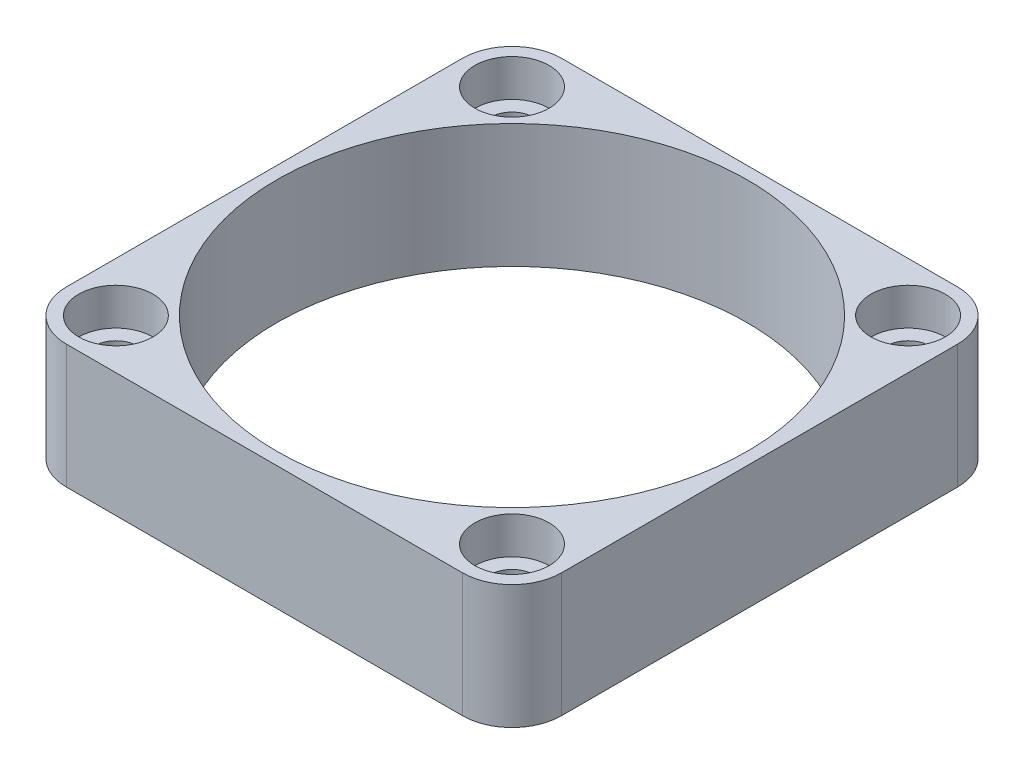
SolidWorks part; units mm, degrees
ref_plane "Front Plane" through (0, 0, 0) normal (0, 0, 1) x (1, 0, 0)
ref_plane "Top Plane" through (0, 0, 0) normal (0, 1, 0) x (1, 0, 0)
ref_plane "Right Plane" through (0, 0, 0) normal (1, 0, 0) x (0, 0, -1)
sketch "Sketch1" plane through (0, 0, 0) normal (0, 1, 0) x (1, 0, 0)
  line L1 (4, 0) -> (36, 0)
  line L2 (0, 4) -> (0, 36)
  line L3 (4, 40) -> (36, 40)
  line L4 (40, 4) -> (40, 36)
  arc A0 (4, 40) -> (0, 36) centre (4, 36) ccw
  arc A1 (0, 4) -> (4, 0) centre (4, 4) ccw
  arc A2 (40, 4) -> (36, 0) centre (36, 4) cw
  arc A3 (40, 36) -> (36, 40) centre (36, 36) ccw
  point P7 (0, 40)
  point P10 (0, 0)
  point P16 (4, 36)
  point P17 (36, 36)
  point P18 (36, 4)
  point P19 (4, 4)
  dimension "D2" = 4
  dimension "D1" = 40
extrude "Boss-Extrude1" add sketch "Sketch1" along normal blind 10
sketch "Sketch2" plane through (0, 10, 0) normal (0, 1, 0) x (1, 0, 0)
  line L0 (20, 0) -> (20, 40) construction
  line L1 (4, 0) -> (36, 0) construction
  line L2 (4, 40) -> (36, 40) construction
  line L3 (0, 20) -> (40, 20) construction
  line L4 (0, 4) -> (0, 36) construction
  line L5 (40, 4) -> (40, 36) construction
  circle A0 centre (4, 4) radius 3
  circle A1 centre (4, 4) radius 1.75
  circle A2 centre (4, 36) radius 1.75
  circle A3 centre (4, 36) radius 3
  circle A4 centre (36, 4) radius 1.75
  circle A5 centre (36, 4) radius 3
  circle A6 centre (36, 36) radius 1.75
  circle A7 centre (36, 36) radius 3
  point P0 (4, 36)
  point P1 (36, 36)
  point P3 (36, 4)
  point P5 (4, 4)
  dimension "D1" = 6
  dimension "D2" = 3.5
extrude "Cut-Extrude1" cut sketch "Sketch2" against normal blind 3 contours A2 | A6 | A7 A6 | A3 A2 | A0 A1 | A1 | A5 A4 | A4 region at (1.0849, 10, -4) region at (4, 10, -4) region at (4, 10, -36) region at (1.0849, 10, -36) region at (36, 10, -4) region at (33.0849, 10, -4) region at (36, 10, -36) region at (33.0849, 10, -36)
extrude "Cut-Extrude2" cut sketch "Sketch2<5>" against normal through all contours A6 | A2 | A1 | A4 region at (4, 10, -4) region at (4, 10, -36) region at (36, 10, -36)
sketch "Sketch2<5>" plane through (0, 10, 0) normal (0, 1, 0) x (1, 0, 0) same geometry as "Sketch2"
sketch "Sketch5" plane through (0, 10, 0) normal (0, 1, 0) x (1, 0, 0)
  line L0 (20, 40) -> (20, 0) construction
  line L1 (36, 40) -> (4, 40) construction
  line L2 (4, 0) -> (36, 0) construction
  line L3 (0, 20) -> (40, 20) construction
  line L4 (0, 36) -> (0, 4) construction
  line L5 (40, 4) -> (40, 36) construction
  circle A0 centre (20, 20) radius 19
  dimension "D1" = 38
extrude "Cut-Extrude3" cut sketch "Sketch5" against normal through all
